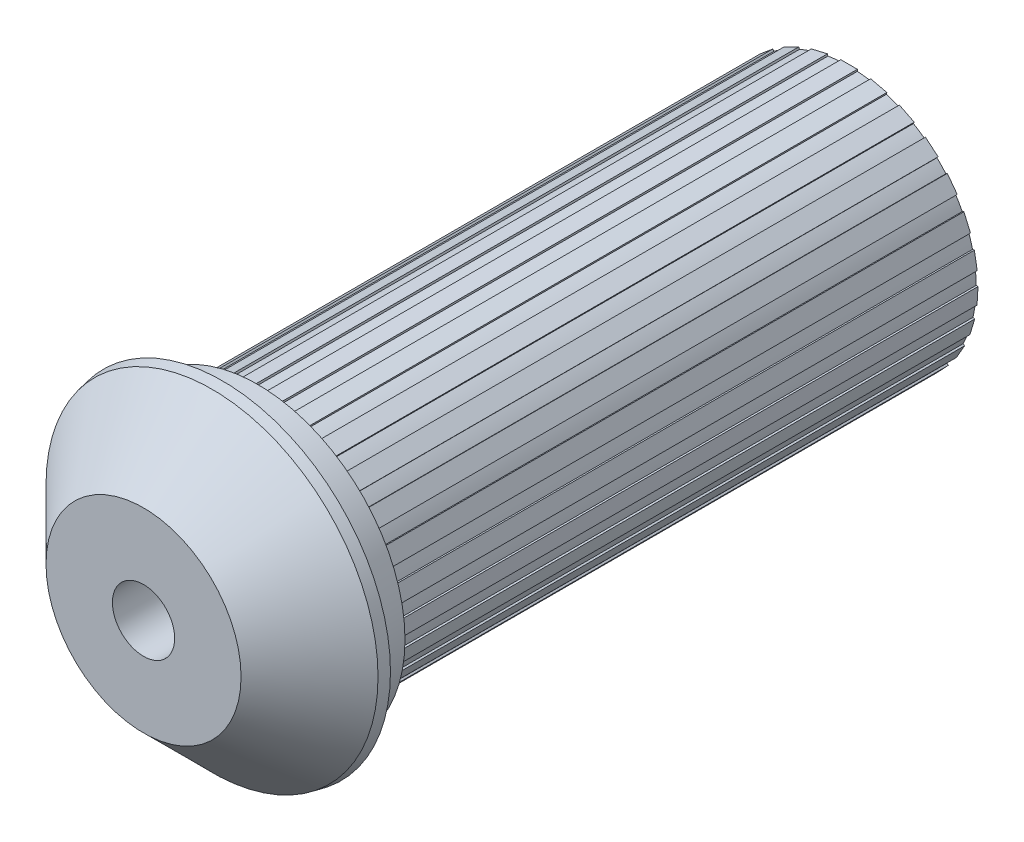
SolidWorks part; units mm, degrees
ref_plane "Front Plane" through (0, 0, 0) normal (0, 0, 1) x (1, 0, 0)
ref_plane "Top Plane" through (0, 0, 0) normal (0, 1, 0) x (1, 0, 0)
ref_plane "Right Plane" through (0, 0, 0) normal (1, 0, 0) x (0, 0, -1)
sketch "Sketch1" plane through (0, 0, 0) normal (0, 0, 1) x (1, 0, 0)
  line L0 (6.2, 2.4) -> (9.8, 2.4) construction
  line L1 (6.2, 2.4) -> (9.8, 2.4)
  arc A0 (6.2, 2.4) -> (9.8, 2.4) centre (8, 0) ccw construction
  arc A1 (6.2, 2.4) -> (9.8, 2.4) centre (8, 0) ccw
  circle A2 centre (8, 0) radius 6.075 construction
  circle A3 centre (8, 0) radius 6.075
  dimension "D1" = 3
  dimension "D2" = 5.4
extrude "Boss-Extrude1" add sketch "Sketch1" along normal up to surface (28.5 mm away)
sketch "Sketch2" plane through (0, 0, 28.5) normal (0, 0, 1) x (1, 0, 0)
  circle A0 centre (8, 0) radius 3
  circle A1 centre (8, 0) radius 1.5
  dimension "D1" = 3
extrude "Boss-Extrude2" add sketch "Sketch2" against normal up to surface (16.5 mm away)
sketch "Sketch3" plane through (0, 0, 28.5) normal (0, 0, 1) x (1, 0, 0)
  circle A0 centre (8, 0) radius 7.1 construction
  circle A1 centre (8, 0) radius 7.1
  circle A2 centre (8, 0) radius 1.5 construction
  circle A3 centre (8, 0) radius 1.5
extrude "Boss-Extrude3" add sketch "Sketch3" along normal offset from surface (5.5 mm away) 22 offset beyond the face yes
chamfer "Chamfer1" [suppressed] distance 1.2 angle 45
chamfer "Chamfer2" distance 2.4 angle 45 1 edges at (15.1, 0, 34)
sketch "Sketch4" plane through (0, 0, 0) normal (0, 0, -1) x (-1, 0, 0)
  circle A0 centre (-8, 0) radius 6.075 construction
  circle A1 centre (-8, 0) radius 6.075
  circle A2 centre (-8, 0) radius 6.125
  dimension "D1" = 12.25
extrude "Boss-Extrude4" add sketch "Sketch4" against normal up to surface (28.5 mm away) up to face at (15.1, 0, 28.5)
sketch "Sketch5" plane through (0, 0, 0) normal (0, 0, -1) x (-1, 0, 0)
  line L0 (-8, 0) -> (-8, 6.125) construction
  line L1 (-8, 0) -> (1.6155, 0) construction
  line L2 (-8.4, 6.05) -> (-7.6, 6.05)
  line L3 (-8.4, 6.05) -> (-8.4, 6.2)
  line L4 (-8.4, 6.2) -> (-7.6, 6.2)
  line L5 (-7.6, 6.05) -> (-7.6, 6.2)
  line L6 (-8.4, 6.05) -> (-7.6, 6.2) construction
  line L7 (-8.4, 6.2) -> (-7.6, 6.05) construction
  circle A0 centre (-8, 0) radius 6.125 construction
  dimension "D1" = 12.4
  dimension "D2" = 0.8
extrude "Boss-Extrude5" add sketch "Sketch5" against normal up to surface (28.5 mm away) up to face at (14.125, 0, 28.5)
pattern_circular "CirPattern1" count 27 over 360 about axis through (8, 0, 0) along (0, 0, 1) of "Boss-Extrude5"
sketch "Sketch6" plane through (0, 0, -27.3) normal (-1, 0, 0) x (0, 1, 0)
  line L0 (0, -61.3) -> (24.9329, -61.3) construction
  line L1 (-4.7, -61.3) -> (4.7, -61.3) construction
  line L2 (27.3, -25.5) -> (50.58, -2.22)
  line L3 (50.58, -2.22) -> (27.3, -2.22)
  line L4 (27.3, -2.22) -> (27.3, -25.5)
  line L5 (2.4, -27.3) -> (-3, -27.3) construction
  line L6 (2.4, -27.3) -> (-3, -27.3) construction
  dimension "D1" = 1.8
  dimension "D2" = 45
revolve "Cut-Revolve1" cut sketch "Sketch6" angle 360 about L0 rebuild error yes
sketch "Sketch7" plane through (0, 0, 0) normal (0, 1, 0) x (1, 0, 0)
  line L0 (8, -34) -> (8, -30.9231) construction
  line L1 (3.3, -34) -> (12.7, -34) construction
  line L2 (0.9, -31.6) -> (0.9, -30.2)
  line L3 (0.9, -28.5) -> (0.9, -31.6) construction
  line L4 (0.9, -30.2) -> (-0.1, -30.2)
  line L5 (-0.1, -30.2) -> (0, -30.7)
  line L6 (0, -30.7) -> (0.9, -31.6)
  line L7 (0.9, -31.6) -> (3.3, -34) construction
  dimension "D1" = 1.4
  dimension "D2" = 0.5
  dimension "D3" = 1
revolve "Revolve1" add sketch "Sketch7" angle 360 about L0
